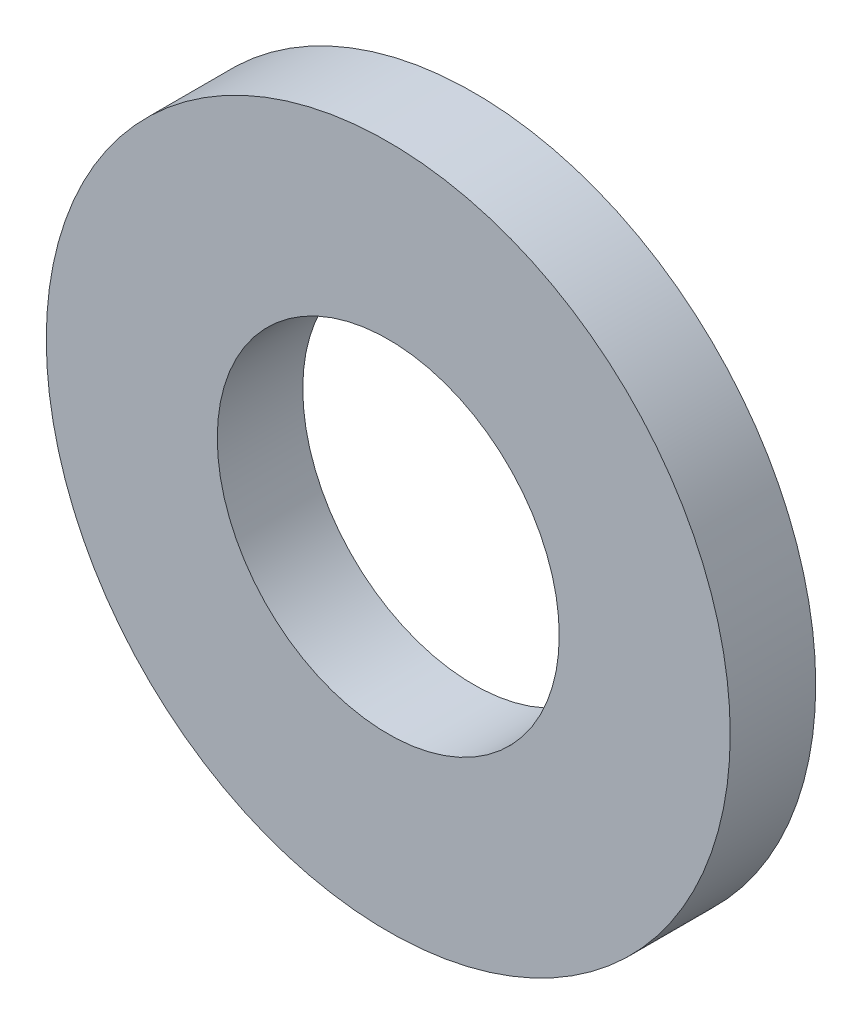
SolidWorks part; units mm, degrees
ref_plane "Front Plane" through (0, 0, 0) normal (0, 0, 1) x (1, 0, 0)
ref_plane "Top Plane" through (0, 0, 0) normal (0, 1, 0) x (1, 0, 0)
ref_plane "Right Plane" through (0, 0, 0) normal (1, 0, 0) x (0, 0, -1)
sketch "Sketch1" plane through (0, 0, 0) normal (0, 0, 1) x (1, 0, 0)
  circle A0 centre (0, 0) radius 6.35
  circle A1 centre (0, 0) radius 12.7
  dimension "D1" = 25.4
  dimension "D2" = 12.7
extrude "Boss-Extrude1" add sketch "Sketch1" along normal blind 3.175
